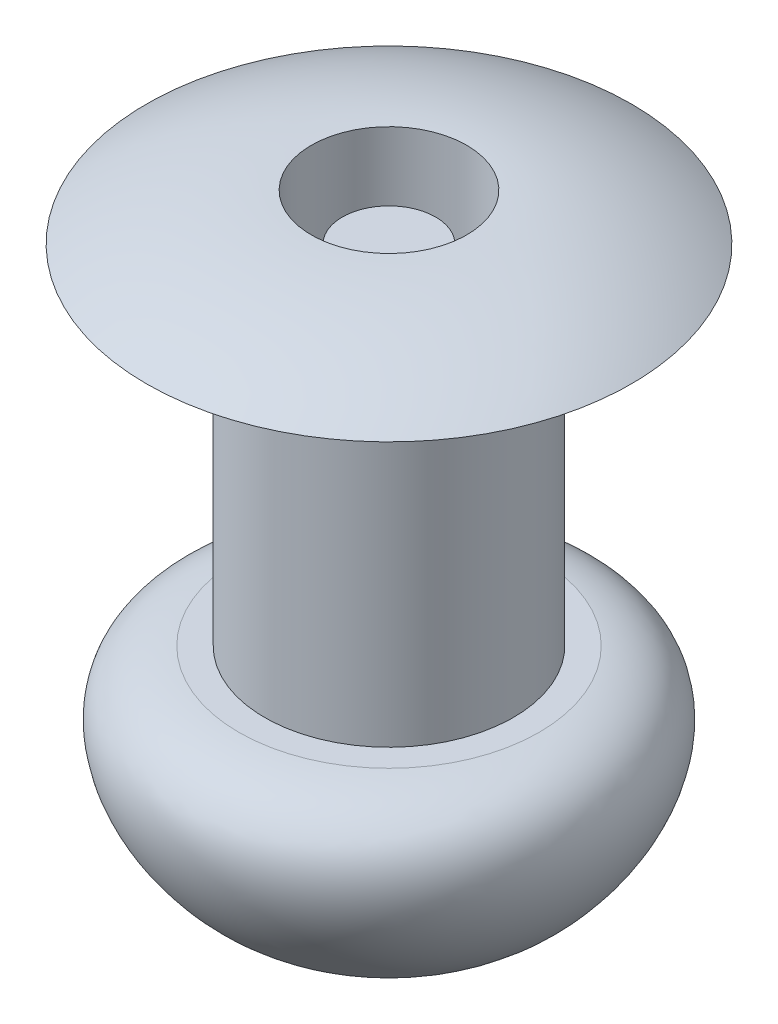
SolidWorks part; units mm, degrees
material "AISI 316 Stal nierdzewna odprężona (SS)"
ref_plane "Płaszczyzna przednia" through (0, 0, 0) normal (0, 0, 1) x (1, 0, 0)
ref_plane "Płaszczyzna górna" through (0, 0, 0) normal (0, 1, 0) x (1, 0, 0)
ref_plane "Płaszczyzna prawa" through (0, 0, 0) normal (1, 0, 0) x (0, 0, -1)
sketch "Szkic1" plane through (0, 0, 0) normal (1, 0, 0) x (0, 0, -1)
  line L0 (0, 0) -> (0, -4.1217)
  line L1 (0, 0) -> (-0.75, 0)
  line L2 (-0.75, 0) -> (-0.75, -5.7984)
  line L3 (-0.75, -5.7984) -> (-1.25, -5.7984)
  line L4 (-1.25, -5.7984) -> (-1.25, 0.75)
  line L5 (-3.9, 0) -> (-2, 0)
  line L6 (-2, 0) -> (-2, -5.5977)
  line L7 (-2, -5.5977) -> (-2.4139, -5.5977)
  line L8 (0, 0) -> (0, 0.4842) construction
  line L9 (0, -5.7984) -> (0, -4.1217)
  line L10 (0, -5.7984) -> (0, -7.2984)
  arc A0 (-1.25, 0.75) -> (-3.9, 0) centre (-1.25, -4.3067) ccw
  ellipse E0 centre (0, -6.5484) end of major axis (-1.75, -6.5484) minor radius 0.75 (-0.956, -7.1766) -> (0, -7.2984) ccw
  spline S0 degree 3 poles (-2.4139, -5.5977) (-3.8675, -5.7674) (-3.5289, -7.8997) (-1.084, -9.4712) (-0.2718, -7.4726) (-0.956, -7.1766) knots 0 0 0 0 0.464993 0.721928 1 1 1 1
  point P14 (1.75, -5.0745)
  point P15 (-1.25, -7.0859)
  point P25 (0, 0)
  dimension "D1" = 7.8
  dimension "D2" = 2.5
  dimension "D3" = 4
  dimension "D4" = 0.75
  dimension "D5" = 1.5
  dimension "D6" = 1.5
  dimension "D7" = 3.5
  dimension "D8" = 3.1855
  dimension "D9" = 2.5026
  dimension "D10" = 1.9
  dimension "D11" = 1.5789
  dimension "D12" = 0.5792
  dimension "D13" = 4.8278
  dimension "D14" = 3.3858
  dimension "D15" = 2.8395
  dimension "D16" = 1.25
  dimension "D17" = 0.6409
  dimension "D18" = 0.956
revolve "Obrót1" add sketch "Szkic1" angle 360 about L8
